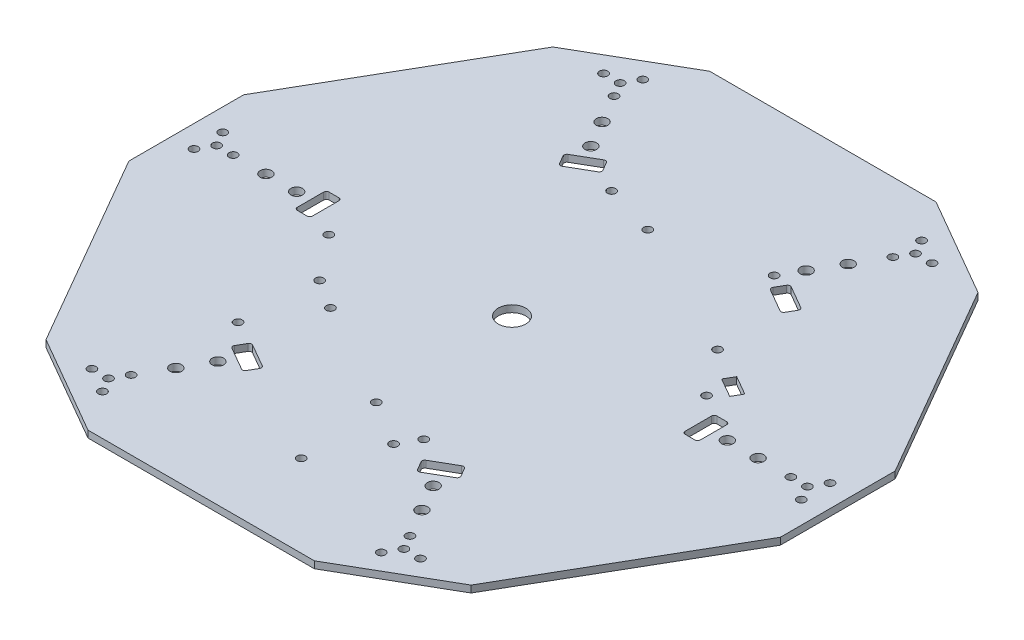
SolidWorks part; units mm, degrees
ref_plane "前视基准面" through (0, 0, 0) normal (0, 0, 1) x (1, 0, 0)
ref_plane "上视基准面" through (0, 0, 0) normal (0, 1, 0) x (1, 0, 0)
ref_plane "右视基准面" through (0, 0, 0) normal (1, 0, 0) x (0, 0, -1)
other "Configuration Table"
sketch "草图2" plane through (0, 0, 0) normal (0, 1, 0) x (1, 0, 0)
  line L1 (45, 0) -> (22.5, 38.9711)
  line L2 (22.5, 38.9711) -> (-22.5, 38.9711)
  line L3 (-22.5, 38.9711) -> (-45, 0)
  line L4 (-45, 0) -> (-22.5, -38.9711)
  line L5 (-22.5, -38.9711) -> (22.5, -38.9711)
  line L6 (22.5, -38.9711) -> (45, 0)
  line L7 (-54.5, 0) -> (-27.25, -47.1984)
  line L8 (-27.25, -47.1984) -> (27.25, -47.1984)
  line L9 (27.25, -47.1984) -> (54.5, 0)
  line L10 (54.5, 0) -> (27.25, 47.1984)
  line L11 (27.25, 47.1984) -> (-27.25, 47.1984)
  line L12 (-27.25, 47.1984) -> (-54.5, 0)
  circle A0 centre (0, 0) radius 38.9711 construction
  circle A1 centre (0, 0) radius 47.1984 construction
  circle A2 centre (0, 0) radius 5
  dimension "D3" = 10
  dimension "D1" = 45
  dimension "D2" = 9.5
extrude "凸台-拉伸1" add sketch "草图2" along normal blind 2.5 contours L5 L6 L1 L2 L3 L4 | L11 L12 L7 L8 L9 L10 L6 L5 L4 L3 L2 L1 region at (32.7189, 0, 18.8903) region at (-39.6262, 0, -22.8782)
sketch "草图3" plane through (0, 2.5, 0) normal (0, 1, 0) x (1, 0, 0)
  line L7 (-45, 0) -> (-22.5, -38.9711) construction
  line L8 (-22.5, -38.9711) -> (22.5, -38.9711) construction
  line L9 (22.5, -38.9711) -> (45, 0) construction
  line L10 (45, 0) -> (22.5, 38.9711) construction
  line L11 (22.5, 38.9711) -> (-22.5, 38.9711) construction
  line L12 (-22.5, 38.9711) -> (-45, 0) construction
  circle A0 centre (0, 0) radius 38.9711 construction
  circle A7 centre (-22.5, 38.9711) radius 2.1
  circle A8 centre (22.5, 38.9711) radius 2.1
  circle A9 centre (45, 0) radius 2.1
  circle A10 centre (22.5, -38.9711) radius 2.1
  circle A11 centre (-22.5, -38.9711) radius 2.1
  circle A12 centre (-45, 0) radius 2.1
  point P23 (0, 0)
  point P24 (0, 0)
  dimension "D2" = 4.2
  dimension "D1" = 45
  dimension "D3" = 6
extrude "切除-拉伸1" [suppressed] cut sketch "草图3" against normal blind 2.5
sketch "草图4" plane through (0, 2.5, 0) normal (0, 1, 0) x (1, 0, 0)
  line L0 (-27.25, 47.1984) -> (-54.5, 0) construction
  line L1 (-54.5, 0) -> (-27.25, -47.1984)
  line L2 (-27.25, -47.1984) -> (27.25, -47.1984)
  line L3 (27.25, -47.1984) -> (54.5, 0)
  line L4 (54.5, 0) -> (27.25, 47.1984)
  line L5 (27.25, 47.1984) -> (-27.25, 47.1984)
  line L6 (-27.25, 47.1984) -> (-54.5, 0)
  line L7 (-100.688, 0) -> (-50.344, -87.1984)
  line L8 (-50.344, -87.1984) -> (50.344, -87.1984)
  line L9 (50.344, -87.1984) -> (100.688, 0)
  line L10 (100.688, 0) -> (50.344, 87.1984)
  line L11 (50.344, 87.1984) -> (-50.344, 87.1984)
  line L12 (-50.344, 87.1984) -> (-100.688, 0)
  circle A0 centre (0, 0) radius 47.1984 construction
  circle A1 centre (0, 0) radius 87.1984 construction
  dimension "D1" = 40
extrude "凸台-拉伸2" add sketch "草图4" against normal up to surface (2.5 mm away) up to face at (0, 0, 5)
sketch "草图5" plane through (0, 2.5, 0) normal (0, 1, 0) x (1, 0, 0)
  line L0 (-50.344, 87.1984) -> (-100.688, 0) construction
  line L1 (-89.141, 0) -> (-44.5705, -77.1984) construction
  line L2 (-44.5705, -77.1984) -> (44.5705, -77.1984) construction
  line L3 (44.5705, -77.1984) -> (89.141, 0) construction
  line L4 (89.141, 0) -> (44.5705, 77.1984) construction
  line L5 (44.5705, 77.1984) -> (-44.5705, 77.1984) construction
  line L6 (-44.5705, 77.1984) -> (-89.141, 0) construction
  circle A0 centre (0, 0) radius 77.1984 construction
  circle A1 centre (-44.5705, 77.1984) radius 2.1
  circle A2 centre (44.5705, 77.1984) radius 2.1
  circle A3 centre (89.141, 0) radius 2.1
  circle A4 centre (44.5705, -77.1984) radius 2.1
  circle A5 centre (-44.5705, -77.1984) radius 2.1
  circle A6 centre (-89.141, 0) radius 2.1
  point P24 (0, 0)
  dimension "D2" = 4.2
  dimension "D1" = 10
  dimension "D3" = 6
extrude "切除-拉伸2" cut sketch "草图5" against normal blind 10
sketch "草图8" plane through (0, 2.5, 0) normal (0, 1, 0) x (1, 0, 0)
  line L0 (50.344, 87.1984) -> (-50.344, 87.1984) construction
  line L1 (-100.688, 0) -> (-50.344, -87.1984) construction
  circle A0 centre (-44.5705, 77.1984) radius 10
  circle A1 centre (44.5705, 77.1984) radius 10
  circle A2 centre (89.141, 0) radius 10
  circle A3 centre (44.5705, -77.1984) radius 10
  circle A4 centre (-44.5705, -77.1984) radius 10
  circle A5 centre (-89.141, 0) radius 10
  circle A6 centre (-113.6008, 65.5875) radius 60
  circle A7 centre (0, 131.175) radius 60
  circle A8 centre (113.6008, 65.5875) radius 60
  circle A9 centre (113.6008, -65.5875) radius 60
  circle A10 centre (0, -131.175) radius 60
  circle A11 centre (-113.6008, -65.5875) radius 60
  point P36 (0, 0)
  line M23 (-50.344, 87.1984) -> (-100.688, 0)
  line M24 (-100.688, 0) -> (-50.344, -87.1984)
  line M25 (-50.344, -87.1984) -> (50.344, -87.1984)
  line M26 (50.344, -87.1984) -> (100.688, 0)
  line M27 (100.688, 0) -> (50.344, 87.1984)
  line M28 (50.344, 87.1984) -> (-50.344, 87.1984)
  dimension "D1" = 120
  dimension "D2" = 6
extrude "切除-拉伸3" cut sketch "草图8" against normal blind 10 contours A0 M28 M23 | A7 A0 M28 | A6 A0 M23 | A7 M28 | A8 M27 | A9 M26 | A10 M25 | A11 M24 | A6 M23 | A1 M27 M28 | A7 A1 M28 | A8 A1 M27 | A8 A2 M27 | A2 M26 M27 | A9 A2 M26 | A9 A3 M26 | A10 A3 M25 | A3 M25 M26 | A11 A4 M24 | A4 M24 M25 | A10 A4 M25 | A5 M23 M24 | A6 A5 M23 | A11 A5 M24 | A6 region at (-41.0716, 2.5, -86.7224) region at (0, 2.5, -80.7095) region at (-54.568, 2.5, -78.9302) region at (-69.8965, 2.5, -40.3547) region at (-49.7383, 2.5, -86.1493) region at (41.0716, 2.5, -86.7224) region at (49.7383, 2.5, -86.1493) region at (54.568, 2.5, -78.9302) region at (69.8965, 2.5, -40.3547) region at (-95.6395, 2.5, -7.7922) region at (95.6395, 2.5, -7.7922) region at (-99.4766, 2.5, 0) region at (99.4766, 2.5, 0) region at (95.6395, 2.5, 7.7922) region at (69.8965, 2.5, 40.3547) region at (-95.6395, 2.5, 7.7922) region at (-69.8965, 2.5, 40.3547) region at (54.568, 2.5, 78.9302) region at (41.0716, 2.5, 86.7224) region at (0, 2.5, 80.7095) region at (-54.568, 2.5, 78.9302) region at (49.7383, 2.5, 86.1493) region at (-41.0716, 2.5, 86.7224) region at (-49.7383, 2.5, 86.1493)
sketch "草图10" plane through (0, 2.5, 0) normal (0, 1, 0) x (1, 0, 0)
  line L0 (-123, 12.1244) -> (-123, -12.1244)
  line L1 (-130, 0) -> (-65, -112.5833)
  line L2 (-65, -112.5833) -> (65, -112.5833)
  line L3 (65, -112.5833) -> (130, 0)
  line L4 (130, 0) -> (65, 112.5833)
  line L5 (65, 112.5833) -> (-65, 112.5833)
  line L6 (-65, 112.5833) -> (-130, 0)
  line L7 (-51, 112.5833) -> (-72, 100.4589)
  line L8 (72, 100.4589) -> (51, 112.5833)
  line L9 (123, -12.1244) -> (123, 12.1244)
  line L10 (51, -112.5833) -> (72, -100.4589)
  line L11 (-72, -100.4589) -> (-51, -112.5833)
  circle A0 centre (0, 0) radius 112.5833 construction
  arc A3 (-38.2033, 84.9093) -> (38.2033, 84.9093) centre (0, 131.175) ccw
  arc A5 (-38.2033, 84.9093) -> (38.2033, 84.9093) centre (0, 131.175) ccw
  arc A17 (-38.2033, 84.9093) -> (-54.432, 75.5397) centre (-44.5705, 77.1984) ccw
  arc A18 (-38.2033, 84.9093) -> (-54.432, 75.5397) centre (-44.5705, 77.1984) ccw
  arc A19 (-92.6353, 9.3696) -> (-54.432, 75.5397) centre (-113.6008, 65.5875) ccw
  arc A20 (-92.6353, 9.3696) -> (-54.432, 75.5397) centre (-113.6008, 65.5875) ccw
  arc A21 (-92.6353, 9.3696) -> (-92.6353, -9.3696) centre (-89.141, 0) ccw
  arc A22 (-92.6353, 9.3696) -> (-92.6353, -9.3696) centre (-89.141, 0) ccw
  arc A23 (-54.432, -75.5397) -> (-92.6353, -9.3696) centre (-113.6008, -65.5875) ccw
  arc A36 (-54.432, -75.5397) -> (-92.6353, -9.3696) centre (-113.6008, -65.5875) ccw
  arc A37 (-54.432, -75.5397) -> (-38.2033, -84.9093) centre (-44.5705, -77.1984) ccw
  arc A38 (-54.432, -75.5397) -> (-38.2033, -84.9093) centre (-44.5705, -77.1984) ccw
  arc A39 (38.2033, -84.9093) -> (-38.2033, -84.9093) centre (0, -131.175) ccw
  arc A40 (38.2033, -84.9093) -> (-38.2033, -84.9093) centre (0, -131.175) ccw
  arc A41 (38.2033, -84.9093) -> (54.432, -75.5397) centre (44.5705, -77.1984) ccw
  arc A42 (38.2033, -84.9093) -> (54.432, -75.5397) centre (44.5705, -77.1984) ccw
  arc A43 (92.6353, -9.3696) -> (54.432, -75.5397) centre (113.6008, -65.5875) ccw
  arc A44 (92.6353, -9.3696) -> (54.432, -75.5397) centre (113.6008, -65.5875) ccw
  arc A45 (92.6353, -9.3696) -> (92.6353, 9.3696) centre (89.141, 0) ccw
  arc A46 (92.6353, -9.3696) -> (92.6353, 9.3696) centre (89.141, 0) ccw
  arc A47 (54.432, 75.5397) -> (92.6353, 9.3696) centre (113.6008, 65.5875) ccw
  arc A48 (54.432, 75.5397) -> (92.6353, 9.3696) centre (113.6008, 65.5875) ccw
  arc A49 (54.432, 75.5397) -> (38.2033, 84.9093) centre (44.5705, 77.1984) ccw
  arc A50 (54.432, 75.5397) -> (38.2033, 84.9093) centre (44.5705, 77.1984) ccw
  point P47 (0, 0)
  arc M32 (38.2033, 84.9093) -> (-38.2033, 84.9093) centre (0, 131.175) cw
  arc M33 (-38.2033, 84.9093) -> (-54.432, 75.5397) centre (-44.5705, 77.1984) ccw
  arc M34 (-54.432, 75.5397) -> (-92.6353, 9.3696) centre (-113.6008, 65.5875) cw
  arc M35 (-92.6353, 9.3696) -> (-92.6353, -9.3696) centre (-89.141, 0) ccw
  arc M36 (-92.6353, -9.3696) -> (-54.432, -75.5397) centre (-113.6008, -65.5875) cw
  arc M37 (-54.432, -75.5397) -> (-38.2033, -84.9093) centre (-44.5705, -77.1984) ccw
  arc M38 (-38.2033, -84.9093) -> (38.2033, -84.9093) centre (0, -131.175) cw
  arc M39 (38.2033, -84.9093) -> (54.432, -75.5397) centre (44.5705, -77.1984) ccw
  arc M40 (54.432, -75.5397) -> (92.6353, -9.3696) centre (113.6008, -65.5875) cw
  arc M41 (92.6353, -9.3696) -> (92.6353, 9.3696) centre (89.141, 0) ccw
  arc M42 (92.6353, 9.3696) -> (54.432, 75.5397) centre (113.6008, 65.5875) cw
  arc M43 (54.432, 75.5397) -> (38.2033, 84.9093) centre (44.5705, 77.1984) ccw
  dimension "D2" = 130
  dimension "D3" = 7
  dimension "D1" = 0
  dimension "D4" = 6
extrude "凸台-拉伸3" add sketch "草图10" against normal up to surface (2.5 mm away) contours L1 L11 L2 L10 L3 L9 L4 L8 L5 L7 L6 L0 M32 M43 M42 M41 M40 M39 M38 M37 M36 M35 M34 M33 region at (-94.6119, 2.5, -54.6242) up to face at (-89.141, 0, 2.1)
sketch "草图11" plane through (0, 2.5, 0) normal (0, 1, 0) x (1, 0, 0)
  line L0 (-123, 12.1244) -> (-123, -12.1244) construction
  line L1 (-123, 0) -> (-107, 0) construction
  line L2 (-107, 0) -> (-101, 0) construction
  circle A0 centre (-107, 0) radius 1.5
  circle A1 centre (-101, 0) radius 1.5
  circle A2 centre (-110, -5.1962) radius 1.5
  circle A3 centre (-110, 5.1962) radius 1.5
  point P12 (-107, 0)
  dimension "D1" = 3
  dimension "D2" = 16
  dimension "D3" = 6
  dimension "D4" = 3
extrude "切除-拉伸4" cut sketch "草图11" against normal through all
pattern_circular "阵列(圆周)1" count 6 over 360 about axis through (0, 2.5, 0) along (0, 1, 0) of "切除-拉伸4"
sketch "草图12" plane through (0, 2.5, 0) normal (0, 1, 0) x (1, 0, 0)
  line L0 (0, 0) -> (60.8571, 0) construction
  line L1 (-118, 68.1273) -> (-118, -68.1273)
  line L2 (-118, -68.1273) -> (0, -136.2547)
  line L3 (0, -136.2547) -> (118, -68.1273)
  line L4 (118, -68.1273) -> (118, 68.1273)
  line L5 (118, 68.1273) -> (0, 136.2547)
  line L6 (0, 136.2547) -> (-118, 68.1273)
  line L7 (-51, 112.5833) -> (-72, 100.4589) construction
  line L9 (-145.896, 84.2331) -> (-145.896, -84.2331)
  line L10 (-145.896, -84.2331) -> (0, -168.4662)
  line L11 (0, -168.4662) -> (145.896, -84.2331)
  line L12 (145.896, -84.2331) -> (145.896, 84.2331)
  line L13 (145.896, 84.2331) -> (0, 168.4662)
  line L14 (0, 168.4662) -> (-145.896, 84.2331)
  circle A0 centre (0, 0) radius 118 construction
  circle A1 centre (0, 0) radius 145.896 construction
  line M51 (-123, -12.1244) -> (-72, -100.4589)
  line M52 (-72, -100.4589) -> (-51, -112.5833)
  line M53 (-51, -112.5833) -> (51, -112.5833)
  line M54 (51, -112.5833) -> (72, -100.4589)
  line M55 (72, -100.4589) -> (123, -12.1244)
  line M56 (123, -12.1244) -> (123, 12.1244)
  line M57 (123, 12.1244) -> (72, 100.4589)
  line M58 (72, 100.4589) -> (51, 112.5833)
  line M59 (51, 112.5833) -> (-51, 112.5833)
  line M60 (-51, 112.5833) -> (-72, 100.4589)
  line M61 (-72, 100.4589) -> (-123, 12.1244)
  line M62 (-123, 12.1244) -> (-123, -12.1244)
  dimension "D1" = 5
extrude "切除-拉伸12" cut sketch "草图12" against normal up to surface (2.5 mm away) contours L13 L14 L9 L10 L11 L12 L6 L5 L4 L3 L2 L1 M59 M58 M57 M56 M55 M54 M53 M52 M51 M62 M61 M60 | L3 M53 M54 M55 | L2 M51 M52 M53 | L1 M61 M62 M51 | L6 M59 M60 M61 | L5 M57 M58 M59 | L4 M55 M56 M57 | L9 L10 L11 L12 L13 L14 | L1 L2 L3 L4 L5 L6 region at (-120.2807, 2.5, 0) region at (-60.1404, 2.5, -104.1661) region at (-60.1404, 2.5, 104.1661) region at (60.1404, 2.5, -104.1661) region at (60.1404, 2.5, 104.1661) region at (120.2807, 2.5, 0) region at (-70.7194, 2.5, -122.4896) up to face at (52.201, 0, -93.4147)
sketch "草图13" plane through (0, 2.5, 0) normal (0, 1, 0) x (1, 0, 0)
  circle A0 centre (-78, 0) radius 2.1
  circle A2 centre (-39, 67.55) radius 2.1
  circle A3 centre (39, 67.55) radius 2.1
  circle A4 centre (78, 0) radius 2.1
  circle A5 centre (39, -67.55) radius 2.1
  circle A6 centre (-39, -67.55) radius 2.1
  point P16 (0, 0)
  dimension "D1" = 4.2
  dimension "D2" = 78
  dimension "D3" = 6
extrude "切除-拉伸13" cut sketch "草图13" against normal blind 10
sketch "草图14" plane through (0, 2.5, 0) normal (0, 1, 0) x (1, 0, 0)
  line L0 (-2.4987, 51.6721) -> (45.9987, 23.6721) construction
  line L1 (45.9987, 23.6721) -> (2.4987, -51.6721) construction
  line L2 (2.4987, -51.6721) -> (-45.9987, -23.6721) construction
  line L3 (-45.9987, -23.6721) -> (-2.4987, 51.6721) construction
  line L4 (0, 0) -> (155.2897, 0) construction
  line L5 (-24.2487, 14) -> (24.2487, -14) construction
  line L6 (45.9987, 23.6721) -> (57.162, 43.0074) construction
  circle A0 centre (-2.4987, 51.6721) radius 1.5
  circle A1 centre (-45.9987, -23.6721) radius 1.5
  circle A2 centre (2.4987, -51.6721) radius 1.5
  circle A3 centre (47.7487, 26.7032) radius 1.5
  dimension "D5" = 3
  dimension "D1" = 30
  dimension "D2" = 28
  dimension "D3" = 87
  dimension "D4" = 28
  dimension "D6" = 3.5
extrude "切除-拉伸14" cut sketch "草图14" against normal blind 10
sketch "草图15" plane through (0, 2.5, 0) normal (0, 1, 0) x (1, 0, 0)
  line L0 (-58.7032, -7.6769) -> (22.7032, -54.6769) construction
  line L1 (22.7032, -54.6769) -> (60.2032, 10.275) construction
  line L2 (60.2032, 10.275) -> (-21.2032, 57.275) construction
  line L3 (-21.2032, 57.275) -> (-58.7032, -7.6769) construction
  line L4 (19.5, 33.775) -> (-18, -31.1769) construction
  line L5 (0, 0) -> (68.6706, 0) construction
  circle A0 centre (-21.2032, 57.275) radius 1.5
  circle A1 centre (60.2032, 10.275) radius 1.5
  circle A2 centre (22.7032, -54.6769) radius 1.5
  circle A3 centre (-58.7032, -7.6769) radius 1.5
  dimension "D3" = 3
  dimension "D1" = 94
  dimension "D2" = 75
  dimension "D4" = 39
  dimension "D5" = 30
extrude "切除-拉伸15" cut sketch "草图15" against normal blind 10
sketch "草图16" plane through (0, 0, 0) normal (0, -1, 0) x (-1, 0, 0)
  line L0 (-57.7175, 18.2197) -> (-64.6457, 14.2197)
  line L1 (-64.6457, 14.2197) -> (-66.6457, 17.6838)
  line L2 (-66.6457, 17.6838) -> (-59.7175, 21.6838)
  line L3 (-59.7175, 21.6838) -> (-57.7175, 18.2197)
  line L4 (45.9987, -23.6721) -> (-2.4987, -51.6721) construction
  line L5 (-39, 67.55) -> (0, 0) construction
  line L6 (-31.75, 54.9926) -> (-52.8668, 42.8008) construction
  line L7 (-22.7032, -54.6769) -> (-6.4532, -82.8227) construction
  line L8 (-6.4532, -82.8227) -> (47.6734, -51.5727) construction
  line L9 (47.6734, -51.5727) -> (31.4234, -23.4269) construction
  line L10 (31.4234, -23.4269) -> (-22.7032, -54.6769) construction
  line L11 (-18.7032, -61.6051) -> (35.4234, -30.3551) construction
  circle A0 centre (-34.75, 60.1888) radius 1.5
  circle A1 centre (-18.7032, -61.6051) radius 1.5
  circle A2 centre (-6.4532, -82.8227) radius 1.5
  circle A3 centre (47.6734, -51.5727) radius 1.5
  circle A4 centre (35.4234, -30.3551) radius 1.5
  dimension "D4" = 3
  dimension "D9" = 3
  dimension "D1" = 8
  dimension "D2" = 4
  dimension "D3" = 14.5
  dimension "D5" = 6
  dimension "D6" = 8
  dimension "D7" = 24.5
  dimension "D8" = 62.5
extrude "切除-拉伸16" cut sketch "草图16" against normal blind 10
sketch "草图17" plane through (0, 0, 0) normal (0, -1, 0) x (1, 0, 0)
  line L0 (-41.4796, 60.3449) -> (-31.5204, 66.0949)
  line L1 (-31.5204, 66.0949) -> (-28.7704, 61.3317)
  line L2 (-28.7704, 61.3317) -> (-38.7296, 55.5817)
  line L3 (-38.7296, 55.5817) -> (-41.4796, 60.3449)
  line L5 (-44.5705, 77.1984) -> (-39, 67.55) construction
  dimension "D1" = 11.5
  dimension "D2" = 5.5
  dimension "D3" = 5
extrude "切除-拉伸17" cut sketch "草图17" against normal blind 10
fillet "圆角1" radius 1 4 edges at (-38.7296, 1.25, 55.5817) (-41.4796, 1.25, 60.3449) (-28.7704, 1.25, 61.3317) (-31.5204, 1.25, 66.0949)
pattern_circular "阵列(圆周)2" count 6 over 360 about axis through (0, 0, 0) along (0, 1, 0) skipping 3 of "圆角1", "切除-拉伸17"
sketch "草图18" plane through (0, 0, 0) normal (0, -1, 0) x (1, 0, 0)
  line L0 (37.7925, -55.4585) -> (40.5425, -60.2216)
  line L1 (40.5425, -60.2216) -> (50.5018, -54.4716)
  line L2 (50.5018, -54.4716) -> (47.7518, -49.7085)
  line L3 (47.7518, -49.7085) -> (37.7925, -55.4585)
  line L4 (34.75, -60.1888) -> (39, -67.55) construction
  dimension "D1" = 11.5
  dimension "D2" = 5.5
  dimension "D3" = 5
extrude "切除-拉伸18" cut sketch "草图18" against normal blind 10
fillet "圆角2" radius 1 4 edges at (40.5425, 1.25, -60.2216) (50.5018, 1.25, -54.4716) (47.7518, 1.25, -49.7085) (37.7925, 1.25, -55.4585)
